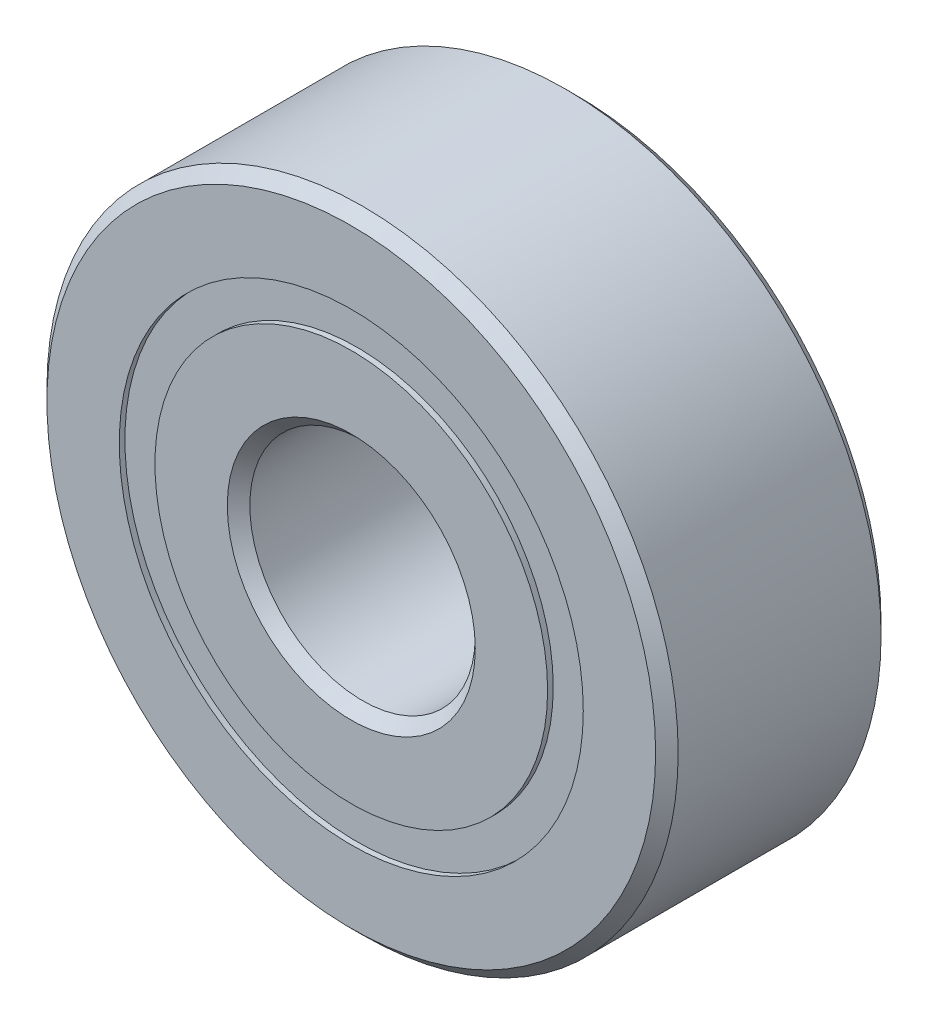
SolidWorks part; units mm, degrees
note: '?' marks a value the reader was unsure of.
ref_plane "Front Plane" through (0, 0, 0) normal (0, 0, 1) x (1, 0, 0)
ref_plane "Top Plane" through (0, 0, 0) normal (0, 1, 0) x (1, 0, 0)
ref_plane "Right Plane" through (0, 0, 0) normal (1, 0, 0) x (0, 0, -1)
sketch "Sketch1" plane through (0, 0, 0) normal (1, 0, 0) x (0, 0, -1)
  line L0 (-2.5, 0) -> (2.5, 0) construction
  line L1 (0, 7) -> (0, -7) construction
  line L2 (2.25, 7) -> (-2.25, 7)
  line L3 (-2.25, 7) -> (-2.5, 6.75)
  line L4 (-2.5, 6.75) -> (-2.5, 5.1456)
  line L5 (-2.5, 5.1456) -> (-1.1111, 5.1456)
  line L6 (2.5, 5.1456) -> (1.1111, 5.1456)
  line L7 (2.5, 6.75) -> (2.5, 5.1456)
  line L8 (2.25, 7) -> (2.5, 6.75)
  line L9 (0, 7) -> (0, 4.75) construction
  line L10 (0, 4.75) -> (0, 2.5) construction
  arc A0 (-1.1111, 5.1456) -> (1.1111, 5.1456) centre (0, 4.75) cw
  point P14 (0, 2.5)
  dimension "D3" = 2.2222
  dimension "D1" = 45
  dimension "Width" = 5
  dimension "OD" = 14
  dimension "D2" = 0.25
  dimension "Shaft Dia" = 5
  dimension "D4" = 0.3956
revolve "Revolve1" add sketch "Sketch1" angle 360 about L0
sketch "Sketch3" plane through (0, 0, 0) normal (1, 0, 0) x (0, 0, -1)
  line L0 (-2.5, 4.3544) -> (-1.1111, 4.3544)
  line L1 (0, 7) -> (0, -7) construction
  line L2 (-2.5, 6.75) -> (-2.5, 5.1456) construction
  line L3 (-2.5, 4.3544) -> (-2.5, 2.75)
  line L4 (-2.25, 7) -> (-2.5, 6.75) construction
  line L5 (-2.5, 2.75) -> (-2.25, 2.5)
  line L6 (-2.25, 2.5) -> (2.25, 2.5)
  line L7 (2.25, 7) -> (2.25, -7) construction
  line L8 (2.25, 2.5) -> (2.5, 2.75)
  line L9 (2.5, -6.75) -> (2.5, 6.75) construction
  line L10 (2.5, 2.75) -> (2.5, 4.3544)
  line L11 (2.5, 4.3544) -> (1.1111, 4.3544)
  line L13 (2.25, 7) -> (2.5, 6.75) construction
  arc A0 (1.1111, 5.1456) -> (-1.1111, 5.1456) centre (0, 4.75) ccw construction
  arc A1 (1.1111, 4.3544) -> (-1.1111, 4.3544) centre (0, 4.75) cw
revolve "Revolve3" add sketch "Sketch3" angle 360 about L0
sketch "Sketch4" plane through (0, 0, 0) normal (1, 0, 0) x (0, 0, -1)
  line L0 (-1.1794, 4.75) -> (1.1794, 4.75)
  arc A2 (-1.1794, 4.75) -> (1.1794, 4.75) centre (0, 4.75) cw
  arc A3 (1.1111, 5.1456) -> (-1.1111, 5.1456) centre (0, 4.75) ccw construction
revolve "Revolve4" add sketch "Sketch4" angle 360 about L0
ref_axis "Axis1" through (0, 0, -2.5) along (0, 0, 1)?
pattern_circular "CirPattern1" count 12 every 30 about axis through (0, 0, 0) along (0, 0, 1) of bodies 104
sketch "Sketch5" plane through (0, 0, 0) normal (1, 0, 0) x (0, 0, -1)
  line L0 (-2.5, 5.1456) -> (-1.1111, 5.1456) construction
  line L1 (-2.375, 5.1456) -> (-1.1794, 5.1456)
  line L2 (-2.375, 5.1456) -> (-2.375, 4.3544)
  line L3 (-2.375, 4.3544) -> (-1.1794, 4.3544)
  line L4 (-1.1794, 5.1456) -> (-1.1794, 4.3544)
  line L5 (-2.5, 4.3544) -> (-1.1111, 4.3544) construction
  line L6 (2.5, 5.1456) -> (1.1111, 5.1456) construction
  line L7 (2.375, 5.1456) -> (1.1794, 5.1456)
  line L8 (2.375, 5.1456) -> (2.375, 4.3544)
  line L9 (2.375, 4.3544) -> (1.1794, 4.3544)
  line L10 (1.1794, 5.1456) -> (1.1794, 4.3544)
  line L11 (2.5, 4.3544) -> (1.1111, 4.3544) construction
  line L12 (-2.25, 7) -> (-2.5, 6.75) construction
  point P18 (-2.375, 6.875)
revolve "Revolve5" add sketch "Sketch5" angle 360 about L0
sketch "Sketch6" plane through (0, 0, 0) normal (1, 0, 0) x (0, 0, -1)
  line L0 (2.5, 0) -> (-2.5, 0) construction
  line L1 (2.5, 5.1456) -> (1.7126, 5.1456)
  line L2 (2.5, 5.1456) -> (2.5, 6.9469)
  line L3 (2.5, 6.9469) -> (1.7126, 6.9469)
  line L4 (1.7126, 5.1456) -> (1.7126, 6.9469)
  dimension "Th" = 0.7874
  dimension "Flange OD" = 13.8938
revolve "Revolve6" [suppressed] add sketch "Sketch6" angle 360 about L0
equation "\"D2@Sketch1\" = \"Width@Sketch1\"*.05"
equation "\"D3@Sketch1\" = \"Width@Sketch1\"/2.25"
equation "\"D4@Sketch1\" = (((\"OD@Sketch1\"-\"Width@Sketch1\")/2)/3.25)/3.5"
equation "\"D2@CirPattern1\" = 360/\"Balls@CirPattern1\""
